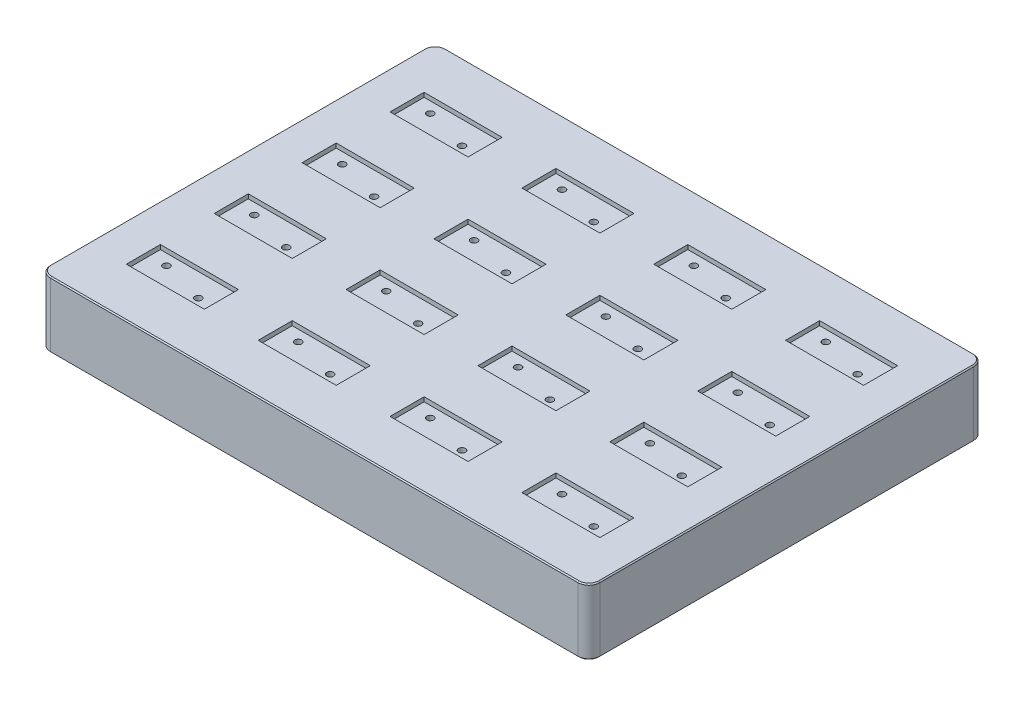
SolidWorks part; units mm, degrees
ref_plane "Front Plane" through (0, 0, 0) normal (0, 0, 1) x (1, 0, 0)
ref_plane "Top Plane" through (0, 0, 0) normal (0, 1, 0) x (1, 0, 0)
ref_plane "Right Plane" through (0, 0, 0) normal (1, 0, 0) x (0, 0, -1)
sketch "Sketch1" plane through (0, 0, 0) normal (0, 1, 0) x (1, 0, 0)
  line L1 (0, 0) -> (250, 0)
  line L2 (0, 0) -> (0, 180)
  line L3 (0, 180) -> (250, 180)
  line L4 (250, 0) -> (250, 180)
  dimension "D1" = 250
  dimension "D2" = 180
extrude "Boss-Extrude1" add sketch "Sketch1" along normal blind 30
sketch "Sketch2" plane through (0, 30, 0) normal (0, 1, 0) x (1, 0, 0)
  line L2 (0, 180) -> (0, 0) construction
  line L3 (17.25, 37.75) -> (52.75, 37.75)
  line L4 (17.25, 37.75) -> (17.25, 22.25)
  line L5 (17.25, 22.25) -> (52.75, 22.25)
  line L6 (52.75, 37.75) -> (52.75, 22.25)
  line L7 (0, 0) -> (250, 0) construction
  dimension "D1" = 15.5
  dimension "D2" = 35.5
  dimension "D3" = 17.25
  dimension "D4" = 22.25
extrude "Cut-Extrude1" cut sketch "Sketch2" against normal blind 2
pattern_linear "LPattern1" count 4 spacing 40 along (0, 0, -1) count 4 spacing 60 along (1, 0, 0) of "Cut-Extrude1"
sketch "Sketch3" plane through (0, 28, 0) normal (0, 1, 0) x (1, 0, 0)
  line L0 (35, 30) -> (35, 37.75) construction
  line L1 (52.75, 37.75) -> (17.25, 37.75) construction
  line L2 (52.75, 37.75) -> (17.25, 37.75) construction
  line L4 (17.25, 22.25) -> (52.75, 22.25) construction
  circle A0 centre (25, 32.75) radius 1.55
  circle A1 centre (45, 27.25) radius 1.55
  dimension "D1" = 3.1
  dimension "D2" = 20
  dimension "D3" = 5
  dimension "D4" = 5
  dimension "D5" = 10
extrude "Cut-Extrude2" cut sketch "Sketch3" against normal through all
pattern_linear "LPattern2" count 4 spacing 40 along (0, 0, -1) count 4 spacing 60 along (1, 0, 0) of "Cut-Extrude2"
sketch "Sketch4" plane through (0, 0, 0) normal (0, -1, 0) x (1, 0, 0)
  line L0 (0, -180) -> (0, 0) construction
  line L1 (3, -3) -> (247, -3)
  line L2 (3, -3) -> (3, -177)
  line L3 (3, -177) -> (247, -177)
  line L4 (247, -3) -> (247, -177)
  line L5 (250, -180) -> (0, -180) construction
  line L6 (250, 0) -> (250, -180) construction
  line L7 (0, 0) -> (250, 0) construction
  dimension "D1" = 3
  dimension "D2" = 3
  dimension "D3" = 3
  dimension "D4" = 3
extrude "Cut-Extrude3" cut sketch "Sketch4" against normal blind 23
fillet "Fillet1" radius 5 4 edges at (0, 15, -180) (0, 15, 0) (250, 15, 0) (250, 15, -180)
chamfer "Chamfer1" distance 0.5 angle 45 16 edges at (0, 0, -90) (1.4645, 0, -1.4645) (1.4645, 0, -178.5355) (125, 0, -180) (248.5355, 0, -1.4645) (248.5355, 0, -178.5355) (250, 0, -90) (0, 30, -90) (1.4645, 30, -1.4645) (1.4645, 30, -178.5355) (125, 30, 0) (125, 30, -180) (248.5355, 30, -1.4645) (248.5355, 30, -178.5355) (250, 30, -90) (125, 0, 0)
sketch "Sketch5" plane through (0, 0, -180) normal (0, 0, -1) x (-1, 0, 0)
  line L0 (0, 29.5) -> (0, 0.5) construction
  line L1 (-36.8, 5) -> (-24.3, 5)
  line L2 (-36.8, 5) -> (-36.8, 16.5)
  line L3 (-36.8, 16.5) -> (-24.3, 16.5)
  line L4 (-24.3, 5) -> (-24.3, 16.5)
  line L5 (-5, 0) -> (-245, 0) construction
  dimension "D1" = 12.5
  dimension "D2" = 11.5
  dimension "D3" = 24.3
  dimension "D4" = 5
extrude "Cut-Extrude4" cut sketch "Sketch5" against normal up to surface (3 mm away) up to face at (125, 11.5, -177)
fillet "Fillet2" radius 4 4 edges at (247, 11.5, -3) (247, 11.5, -177) (3, 11.5, -177) (3, 11.5, -3)
sketch "Sketch7" plane through (0, 23, 0) normal (0, -1, 0) x (1, 0, 0)
  line L0 (245, -180) -> (5, -180) construction
  line L1 (0, -175) -> (0, -5) construction
  circle A0 centre (17.78, -83.48) radius 3
  circle A1 centre (66.04, -77.13) radius 3
  circle A2 centre (60.96, -107.61) radius 3
  circle A3 centre (33.02, -107.61) radius 3
  circle A4 centre (17.78, -158.41) radius 3
  circle A5 centre (66.04, -159.68) radius 3
  dimension "D1" = 6
  dimension "D2" = 48.26
  dimension "D3" = 24.13
  dimension "D4" = 27.94
  dimension "D5" = 50.8
  dimension "D6" = 48.26
  dimension "D7" = 21.59
  dimension "D8" = 17.78
  dimension "D9" = 17.78
  dimension "D10" = 33.02
  dimension "D11" = 102.87
  dimension "D12" = 20.32
extrude "Boss-Extrude2" add sketch "Sketch7" along normal blind 5
fillet "Fillet3" radius 2 6 edges at (17.78, 23, -161.41) (66.04, 23, -162.68) (66.04, 23, -80.13) (60.96, 23, -110.61) (33.02, 23, -110.61) (17.78, 23, -86.48)
sketch "Sketch8" plane through (0, 18, 0) normal (0, -1, 0) x (1, 0, 0)
  circle A0 centre (17.78, -83.48) radius 1.3
  circle A1 centre (66.04, -77.13) radius 1.3
  circle A2 centre (60.96, -107.61) radius 1.3
  circle A3 centre (33.02, -107.61) radius 1.3
  circle A4 centre (17.78, -158.41) radius 1.3
  circle A5 centre (66.04, -159.68) radius 1.3
  dimension "D1" = 2.6
extrude "Cut-Extrude5" cut sketch "Sketch8" against normal blind 6
sketch "Sketch9" plane through (0, 0, -177) normal (0, 0, 1) x (1, 0, 0)
  line L4 (216.3, 17.35) -> (180.9, 17.35)
  line L5 (178.6349, 14.6506) -> (179.9697, 7.0806)
  line L6 (182.2348, 5.18) -> (214.9652, 5.18)
  line L7 (217.2303, 7.0806) -> (218.5651, 14.6506)
  circle A4 centre (222.1, 11.265) radius 1.6
  circle A5 centre (175.1, 11.265) radius 1.6
  arc A6 (180.9, 17.35) -> (178.6349, 14.6506) centre (180.9, 15.05) ccw
  arc A7 (179.9697, 7.0806) -> (182.2348, 5.18) centre (182.2348, 7.48) ccw
  arc A8 (214.9652, 5.18) -> (217.2303, 7.0806) centre (214.9652, 7.48) ccw
  arc A9 (218.5651, 14.6506) -> (216.3, 17.35) centre (216.3, 15.05) ccw
extrude "Cut-Extrude6" cut sketch "Sketch9" against normal up to surface (3 mm away) up to face at (30.55, 10.75, -180)
sketch "Sketch11" plane through (0, 23, 0) normal (0, -1, 0) x (1, 0, 0)
  line L0 (0.5, -90) -> (-8.3083, -90) construction
  line L1 (0.5, -5) -> (0.5, -175) construction
  line L2 (0, -175) -> (0, -5) construction
  line L3 (5, 0) -> (245, 0) construction
  line L4 (250, -5) -> (250, -175) construction
  line L5 (245, -180) -> (5, -180) construction
  line L6 (2.5, -90) -> (-6.231, -90) construction
  line L7 (125, -2.5) -> (125, 16.271) construction
  line L8 (125, -179.5) -> (125, -189.3502) construction
  line L9 (5, -179.5) -> (245, -179.5) construction
  circle A0 centre (7.5, -7.5) radius 5
  circle A1 centre (242.5, -7.5) radius 5
  circle A2 centre (242.5, -172.5) radius 5
  circle A3 centre (7.5, -172.5) radius 5
  circle A4 centre (125, -7.5) radius 5
  circle A5 centre (242.5, -90) radius 5
  circle A6 centre (7.5, -90) radius 5
  circle A7 centre (125, -172.5) radius 5
  dimension "D1" = 10
  dimension "D4" = 7.5
  dimension "D2" = 7.5
  dimension "D3" = 7.5
  dimension "D5" = 7.5
extrude "Boss-Extrude3" add sketch "Sketch11" along normal blind 21
sketch "Sketch12" plane through (0, 2, 0) normal (0, -1, 0) x (1, 0, 0)
  circle A0 centre (7.5, -90) radius 1.25
  circle A1 centre (7.5, -7.5) radius 1.25
  circle A2 centre (125, -7.5) radius 1.25
  circle A3 centre (242.5, -7.5) radius 1.25
  circle A4 centre (242.5, -90) radius 1.25
  circle A5 centre (242.5, -172.5) radius 1.25
  circle A6 centre (125, -172.5) radius 1.25
  circle A7 centre (7.5, -172.5) radius 1.25
  dimension "D1" = 2.5
extrude "Cut-Extrude7" cut sketch "Sketch12" against normal blind 10
fillet "Fillet4" radius 1 16 edges at (3, 12.5, -9.6794) (9.6794, 12.5, -3) (127.1794, 12.5, -3) (122.8206, 12.5, -3) (240.3206, 12.5, -3) (247, 12.5, -9.6794) (247, 12.5, -92.1794) (247, 12.5, -87.8206) (247, 12.5, -170.3206) (240.3206, 12.5, -177) (122.8206, 12.5, -177) (127.1794, 12.5, -177) (9.6794, 12.5, -177) (3, 12.5, -170.3206) (3, 12.5, -87.8206) (3, 12.5, -92.1794)
